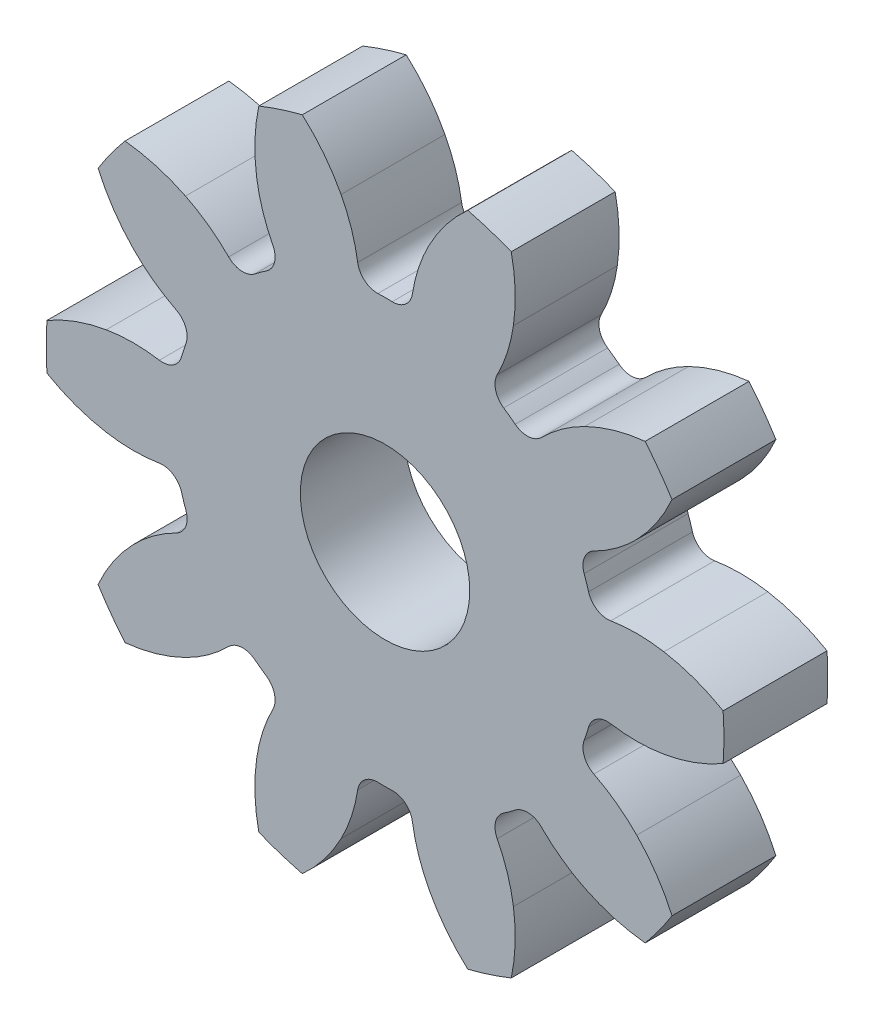
SolidWorks part; units mm, degrees
ref_plane "Front Plane" through (0, 0, 0) normal (0, 0, 1) x (1, 0, 0)
ref_plane "Top Plane" through (0, 0, 0) normal (0, 1, 0) x (1, 0, 0)
ref_plane "Right Plane" through (0, 0, 0) normal (1, 0, 0) x (0, 0, -1)
sketch "Sketch1" plane through (0, 0, 0) normal (0, 0, 1) x (1, 0, 0)
  line L0 (0, 0) -> (15.875, 0) construction
  line L1 (15.875, 0) -> (19.05, 0) construction
  circle A0 centre (0, 0) radius 19.05
  circle A1 centre (0, 0) radius 15.875 construction
  dimension "D2" = 31.75
  dimension "D1" = 3.175
extrude "GEAR_BASE" add sketch "Sketch1" along normal mid plane 5.842
sketch "Sketch2" plane through (0, 0, 2.921) normal (0, 0, 1) x (1, 0, 0)
  line L0 (0, 0) -> (11.9062, 0) construction
  line L1 (11.9062, 0) -> (15.875, 0) construction
  line L2 (0, 0) -> (-19.05, 0) construction
  line L3 (0, 0) -> (-15.6779, -2.494) construction
  line L4 (-15.6779, -2.494) -> (-17.3322, 7.9056) construction
  line L5 (0, 0) -> (-15.4118, -11.1973) construction
  line L6 (-15.6779, -2.494) -> (-11.6427, -2.4912) construction
  line L7 (-14.1496, -7.1976) -> (-10.8835, -4.8279) construction
  line L8 (0, 0) -> (-14.1496, -7.1976) construction
  line L9 (-15.6779, -2.494) -> (-19.0066, -1.2849) construction
  line L10 (-14.1496, -7.1976) -> (-16.1319, -10.1323) construction
  line L11 (-14.1496, -7.1976) -> (-12.6837, -9.2152) construction
  line L12 (-14.1496, -7.1976) -> (-9.3753, -16.5833) construction
  line L13 (-15.6779, -2.494) -> (-15.6779, 0) construction
  circle A0 centre (0, 0) radius 15.875 construction
  circle A1 centre (0, 0) radius 11.9062 construction
  circle A2 centre (0, 0) radius 19.05 construction
  arc A3 (-16.1319, -10.1323) -> (-19.0066, -1.2849) centre (0, 0) cw
  arc A4 (-11.4411, -3.2955) -> (-12.6878, -2.5063) centre (-12.5089, -3.6031) ccw
  arc A5 (-11.7378, -5.43) -> (-11.1931, -4.0588) centre (-12.2378, -4.4376) ccw
  arc A6 (-11.1931, -4.0588) -> (-11.4411, -3.2955) centre (0, 0) cw
  arc A7 (-16.1319, -10.1323) -> (-14.1496, -7.1976) centre (-7.0054, -14.1602) cw
  arc A8 (-19.0066, -1.2849) -> (-15.6779, -2.494) centre (-13.9907, 7.3382) ccw
  arc A9 (-14.1496, -7.1976) -> (-11.7378, -5.43) centre (-7.6627, -13.5197) cw
  arc A10 (-15.6779, -2.494) -> (-12.6878, -2.5063) centre (-14.1459, 6.4336) ccw
  dimension "D1" = 31.75
  dimension "D11" = 1.1112
  dimension "D12" = 9.9758
  dimension "D2" = 3.9688
  dimension "D3" = 36
  dimension "D5" = 9
  dimension "D7" = 9
  dimension "D8" = 4.9457
  dimension "D9" = 20
  dimension "D10" = 20
  dimension "D6" = 2.494
  dimension "D4" = 2.494
extrude "GEAR_CUT" cut sketch "Sketch2" against normal through all
ref_axis "GEAR_AXIS" through (0, 0, -3.2131) along (0, 0, 1)
pattern_circular "GEAR_TEETH" count 10 over 360 about axis through (0, 0, -3.2131) along (0, 0, 1) of "GEAR_CUT"
sketch "Sketch3" plane through (0, 0, 2.921) normal (0, 0, 1) x (1, 0, 0)
  circle A0 centre (0, 0) radius 4.7625
  dimension "D1" = 9.525
extrude "BORE" cut sketch "Sketch3" against normal through all
equation "\"N_teeth\"= 10"
equation "\"pitch_diameter\"= \"N_teeth\" / \"Pitch\""
equation "\"Pitch\"= 8"
equation "\"addendum\"=1.000/\"Pitch\""
equation "\"face_width\"=0.23"
equation "\"deddendum\"=1.250/\"Pitch\""
equation "\"tooth_thickness\"=1.571/\"Pitch\""
equation "\"Pressure_Angle\"=20.000000"
equation "\"base_fillet\"=0.35/\"Pitch\""
equation "\"D1@Sketch1\"=\"addendum\""
equation "\"D2@Sketch1\"=\"pitch_diameter\""
equation "\"D1@GEAR_BASE\" = \"face_width\""
equation "\"D1@Sketch2\"= \"pitch_diameter\""
equation "\"D2@Sketch2\"=\"deddendum\""
equation "\"D4@Sketch2\"=\"tooth_thickness\"/2"
equation "\"D6@Sketch2\"=\"tooth_thickness\"/2"
equation "\"D9@Sketch2\"=\"Pressure_Angle\""
equation "\"D10@Sketch2\"=\"Pressure_Angle\""
equation "\"D11@Sketch2\"=\"base_fillet\""
equation "\"D12@Sketch2\"=2*\"tooth_thickness\""
equation "\"D3@Sketch2\" = 360 / \"N_teeth\""
equation "\"D1@GEAR_TEETH\" = \"N_teeth\""
